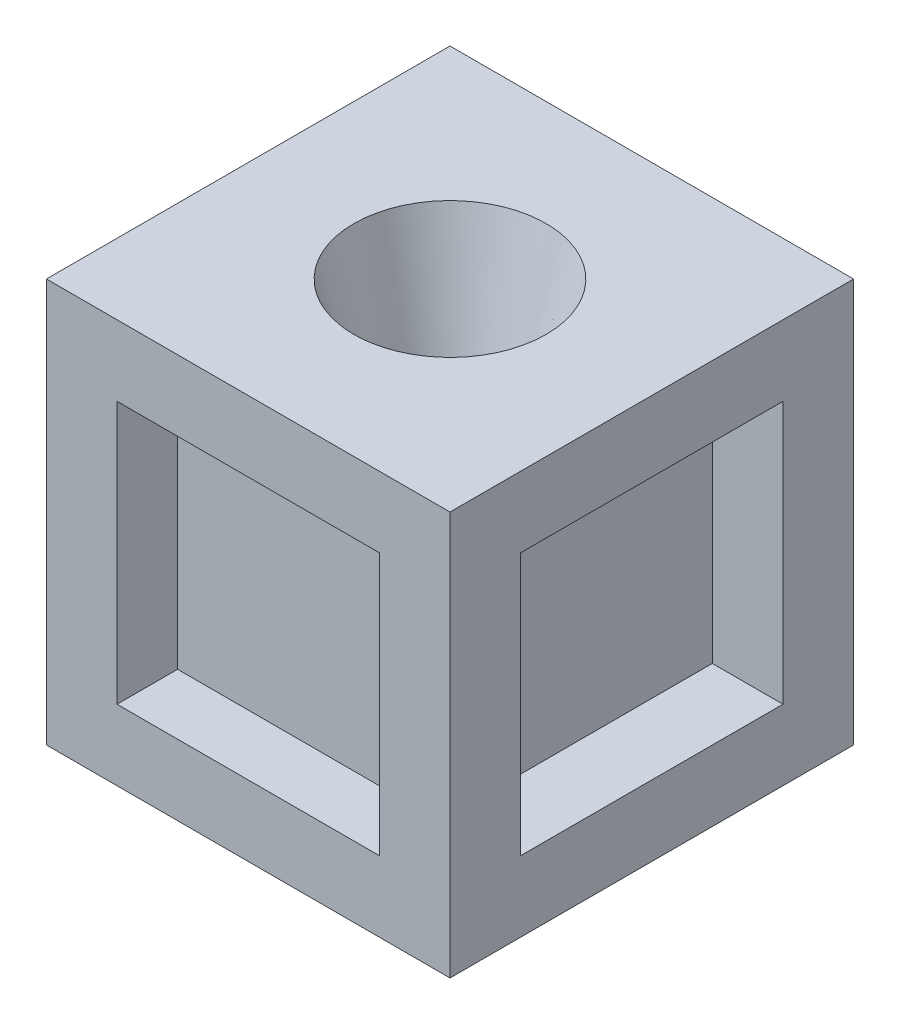
SolidWorks part; units mm, degrees
ref_plane "Plano frontal" through (0, 0, 0) normal (0, 0, 1) x (1, 0, 0)
ref_plane "Plano superior" through (0, 0, 0) normal (0, 1, 0) x (1, 0, 0)
ref_plane "Plano direito" through (0, 0, 0) normal (1, 0, 0) x (0, 0, -1)
sketch "Esboço1" plane through (0, 0, 0) normal (0, 1, 0) x (1, 0, 0)
  line L1 (-33.7032, -8.1007) -> (6.2968, -8.1007)
  line L2 (-33.7032, -8.1007) -> (-33.7032, -48.1007)
  line L3 (-33.7032, -48.1007) -> (6.2968, -48.1007)
  line L4 (6.2968, -8.1007) -> (6.2968, -48.1007)
extrude "Ressalto-extrusão1" add sketch "Esboço1" along normal blind 40
sketch "Esboço2" plane through (0, 40, 0) normal (0, 1, 0) x (1, 0, 0)
  line L0 (6.2968, -8.1007) -> (-33.7032, -8.1007) construction
  line L1 (6.2968, -48.1007) -> (6.2968, -8.1007) construction
  circle A0 centre (-13.7032, -28.1007) radius 9.523
  dimension "D1" = 20
  dimension "D2" = 20
ref_plane "Plano1" through (0, 11.42, 0) normal (0, 1, 0) x (1, 0, 0)
sketch "Esboço4" plane through (0, 11.42, 0) normal (0, 1, 0) x (1, 0, 0)
  circle A0 centre (-13.7032, -28.1007) radius 3.5
loft "Loft de corte4" cut profiles "Esboço2", "Esboço4" connector at (-11.1442, 40, 18.928) connector at (-10.3807, 11.42, 27.0003)
fillet "Filete1" radius 1 1 edges at (-13.7032, 11.42, 31.6007)
sketch "Esboço10" plane through (-33.7032, 0, 0) normal (-1, 0, 0) x (0, 0, 1)
  line L1 (41.1007, 33) -> (15.1007, 33)
  line L2 (41.1007, 33) -> (41.1007, 7)
  line L3 (41.1007, 7) -> (15.1007, 7)
  line L4 (15.1007, 33) -> (15.1007, 7)
  line L5 (8.1007, 0) -> (48.1007, 0) construction
  line L6 (48.1007, 40) -> (48.1007, 0) construction
  line L7 (8.1007, 40) -> (8.1007, 0) construction
  dimension "D2" = 7
  dimension "D3" = 7
  dimension "D4" = 7
extrude "Corte-extrusão3" cut sketch "Esboço10" against normal blind 7
sketch "Esboço11" plane through (0, 0, 8.1007) normal (0, 0, -1) x (-1, 0, 0)
  line L0 (-6.2968, 40) -> (-6.2968, 0) construction
  line L1 (0.7032, 33) -> (26.7032, 33)
  line L2 (0.7032, 33) -> (0.7032, 7)
  line L3 (0.7032, 7) -> (26.7032, 7)
  line L4 (26.7032, 33) -> (26.7032, 7)
  line L5 (33.7032, 40) -> (33.7032, 0) construction
  line L7 (-6.2968, 0) -> (33.7032, 0) construction
  dimension "D1" = 7
  dimension "D2" = 7
  dimension "D4" = 7
extrude "Corte-extrusão6" cut sketch "Esboço11" against normal blind 6
sketch "Esboço12" plane through (0, 0, 48.1007) normal (0, 0, 1) x (1, 0, 0)
  line L0 (-33.7032, 40) -> (-33.7032, 0) construction
  line L1 (-26.7032, 33) -> (-0.7032, 33)
  line L2 (-26.7032, 33) -> (-26.7032, 7)
  line L3 (-26.7032, 7) -> (-0.7032, 7)
  line L4 (-0.7032, 33) -> (-0.7032, 7)
  line L6 (6.2968, 40) -> (6.2968, 0) construction
  line L7 (-33.7032, 0) -> (6.2968, 0) construction
  dimension "D1" = 7
  dimension "D3" = 7
  dimension "D4" = 7
extrude "Corte-extrusão7" cut sketch "Esboço12" against normal blind 6
sketch "Esboço13" plane through (6.2968, 0, 0) normal (1, 0, 0) x (0, 0, -1)
  line L1 (-41.1007, 33) -> (-15.1007, 33)
  line L2 (-41.1007, 33) -> (-41.1007, 7)
  line L3 (-41.1007, 7) -> (-15.1007, 7)
  line L4 (-15.1007, 33) -> (-15.1007, 7)
  line L5 (-48.1007, 40) -> (-48.1007, 0) construction
  line L6 (-48.1007, 0) -> (-8.1007, 0) construction
  line L7 (-8.1007, 40) -> (-8.1007, 0) construction
  dimension "D2" = 7
  dimension "D3" = 7
  dimension "D4" = 7
extrude "Corte-extrusão8" cut sketch "Esboço13" against normal blind 7
